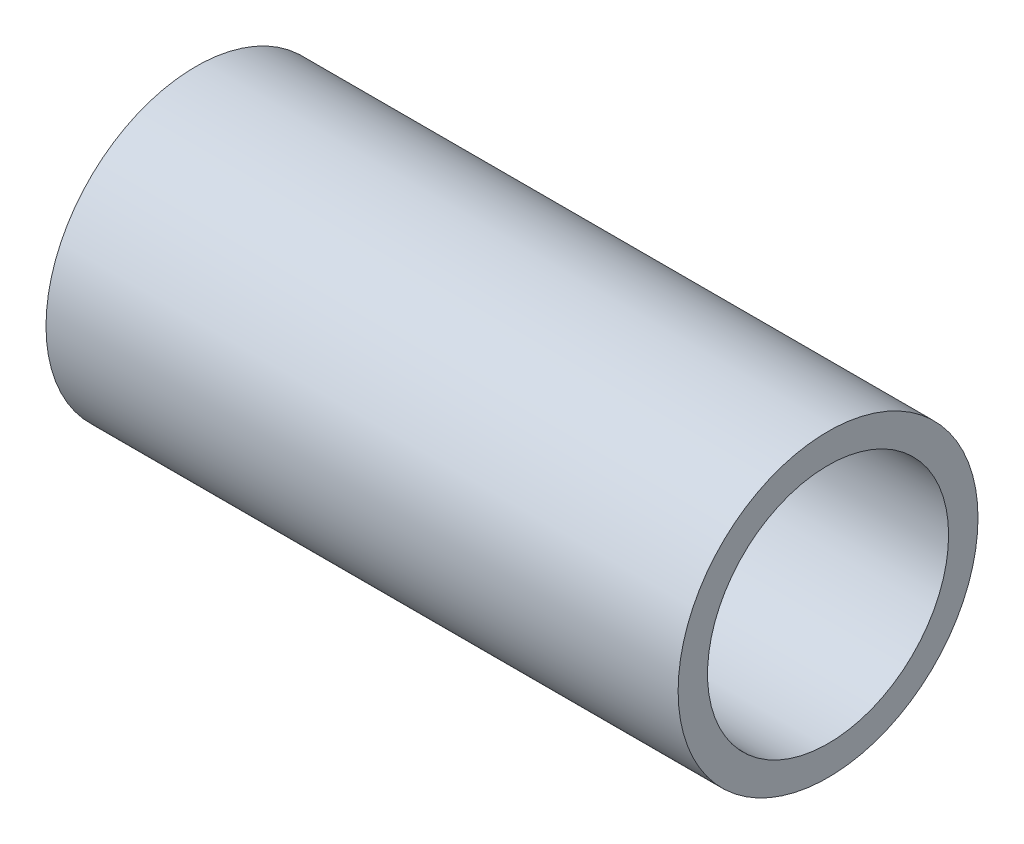
SolidWorks part; units mm, degrees
ref_plane "Vorne" through (0, 0, 0) normal (0, 0, 1) x (1, 0, 0)
ref_plane "Oben" through (0, 0, 0) normal (0, 1, 0) x (1, 0, 0)
ref_plane "Seite" through (0, 0, 0) normal (1, 0, 0) x (0, 0, -1)
sketch "Skizze1" plane through (0, 0, 0) normal (1, 0, 0) x (0, 0, -1)
  circle A0 centre (0, 0) radius 2.05
  circle A1 centre (0, 0) radius 2.55
  dimension "D1" = 4.1
  dimension "D2" = 5.1
extrude "Aufsatz-Linear austragen1" add sketch "Skizze1" along normal blind 10.75
